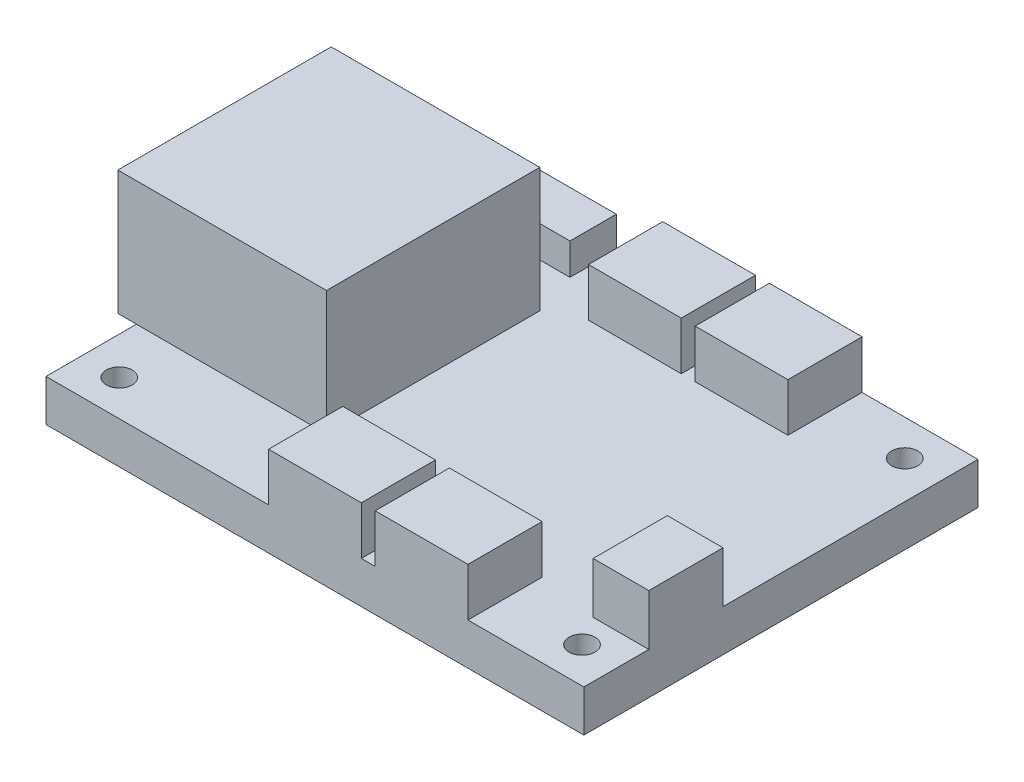
SolidWorks part; units mm, degrees
ref_plane "Front Plane" through (0, 0, 0) normal (0, 0, 1) x (1, 0, 0)
ref_plane "Top Plane" through (0, 0, 0) normal (0, 1, 0) x (1, 0, 0)
ref_plane "Right Plane" through (0, 0, 0) normal (1, 0, 0) x (0, 0, -1)
sketch "Sketch1" plane through (0, 0, 0) normal (0, 1, 0) x (1, 0, 0)
  line L0 (0, 21.25) -> (0, -21.25) construction
  line L1 (-29, -21.25) -> (29, -21.25)
  line L2 (-29, -21.25) -> (-29, 21.25)
  line L3 (-29, 21.25) -> (29, 21.25)
  line L4 (29, -21.25) -> (29, 21.25)
  line L5 (-29, -21.25) -> (29, 21.25) construction
  line L6 (-29, 21.25) -> (29, -21.25) construction
  line L7 (-29, 0) -> (29, 0) construction
  circle A0 centre (-24.95, 17.4) radius 1.4
  circle A1 centre (24.95, 17.4) radius 1.4
  circle A2 centre (24.95, -17.4) radius 1.4
  circle A3 centre (-24.95, -17.4) radius 1.4
  point P0 (0, 0)
  dimension "D3" = 2.8
  dimension "D1" = 58
  dimension "D2" = 42.5
  dimension "D4" = 49.9
  dimension "D5" = 34.8
extrude "Boss-Extrude1" add sketch "Sketch1" along normal blind 4.5
sketch "Sketch2" plane through (0, 4.5, 0) normal (0, 1, 0) x (1, 0, 0)
  line L0 (-29, 0) -> (12, 0) construction
  line L1 (-31, 11.5) -> (-8.5, 11.5)
  line L2 (-31, 11.5) -> (-31, -11.5)
  line L3 (-31, -11.5) -> (-8.5, -11.5)
  line L4 (-8.5, 11.5) -> (-8.5, -11.5)
  line L5 (-29, 21.25) -> (-29, -21.25) construction
  line L6 (29, 21.25) -> (-29, 21.25) construction
  line L7 (-5, 21.25) -> (5, 21.25)
  line L8 (-5, 21.25) -> (-5, 13.25)
  line L9 (-5, 13.25) -> (5, 13.25)
  line L10 (5, 21.25) -> (5, 13.25)
  line L11 (5.75, 21.25) -> (5.75, -21.25) construction
  line L12 (-29, -21.25) -> (29, -21.25) construction
  line L13 (16.5, 21.25) -> (16.5, 13.25)
  line L14 (16.5, 21.25) -> (6.5, 21.25)
  line L15 (6.5, 21.25) -> (6.5, 13.25)
  line L16 (16.5, 13.25) -> (6.5, 13.25)
  line L17 (16.5, -21.25) -> (6.5, -21.25)
  line L18 (16.5, -21.25) -> (16.5, -13.25)
  line L19 (16.5, -13.25) -> (6.5, -13.25)
  line L20 (6.5, -21.25) -> (6.5, -13.25)
  line L21 (5, -21.25) -> (5, -13.25)
  line L22 (-5, -21.25) -> (5, -21.25)
  line L23 (-5, -21.25) -> (-5, -13.25)
  line L24 (-5, -13.25) -> (5, -13.25)
  line L25 (29, -21.25) -> (29, 21.25) construction
  line L26 (29, -6.25) -> (23, -6.25)
  line L27 (29, -6.25) -> (29, -14.25)
  line L28 (29, -14.25) -> (23, -14.25)
  line L29 (23, -6.25) -> (23, -14.25)
  line L31 (-19, 21.25) -> (-10, 21.25)
  line L32 (-19, 21.25) -> (-19, 16.25)
  line L33 (-19, 16.25) -> (-10, 16.25)
  line L34 (-10, 21.25) -> (-10, 16.25)
  point P9 (-8.5, 0)
  line M16 (29, -21.25) -> (29, 21.25)
  line M17 (29, 21.25) -> (-29, 21.25)
  line M18 (-29, 21.25) -> (-29, -21.25)
  line M19 (-29, -21.25) -> (29, -21.25)
  dimension "D1" = 22.5
  dimension "D2" = 23
  dimension "D3" = 2
  dimension "D4" = 8
  dimension "D5" = 10
  dimension "D6" = 24
  dimension "D7" = 0.75
  dimension "D8" = 8
  dimension "D9" = 6
  dimension "D10" = 7
  dimension "D11" = 9
  dimension "D12" = 5
  dimension "D13" = 10
extrude "Boss-Extrude2" add sketch "Sketch2" along normal blind 13.4 contours L4 L1 L3 M18 | L2 L3 L1 M18 region at (-30, 4.5, 0) region at (-18.75, 4.5, 0)
extrude "Boss-Extrude3" add sketch "Sketch2<3>" along normal blind 5.2 contours L10 L8 L9 M17 | L16 L13 L15 M17 | L24 L23 L21 M19 | L20 L18 L19 M19 region at (11.5, 4.5, -17.25) region at (0, 4.5, -17.25) region at (0, 4.5, 17.25) region at (11.5, 4.5, 17.25)
sketch "Sketch2<3>" plane through (0, 4.5, 0) normal (0, 1, 0) x (1, 0, 0) same geometry as "Sketch2"
extrude "Boss-Extrude4" add sketch "Sketch2<4>" along normal blind 5.5 contours L26 L29 L28 M16 region at (26, 4.5, 10.25)
sketch "Sketch2<4>" plane through (0, 4.5, 0) normal (0, 1, 0) x (1, 0, 0) same geometry as "Sketch2"
extrude "Boss-Extrude5" add sketch "Sketch2<5>" along normal blind 3.4 contours L34 L32 L33 M17 region at (-14.5, 4.5, -18.75)
sketch "Sketch2<5>" plane through (0, 4.5, 0) normal (0, 1, 0) x (1, 0, 0) same geometry as "Sketch2"
equation "\"D4@Sketch1\"=47.1+\"D3@Sketch1\""
equation "\"D5@Sketch1\"=32+\"D3@Sketch1\""
